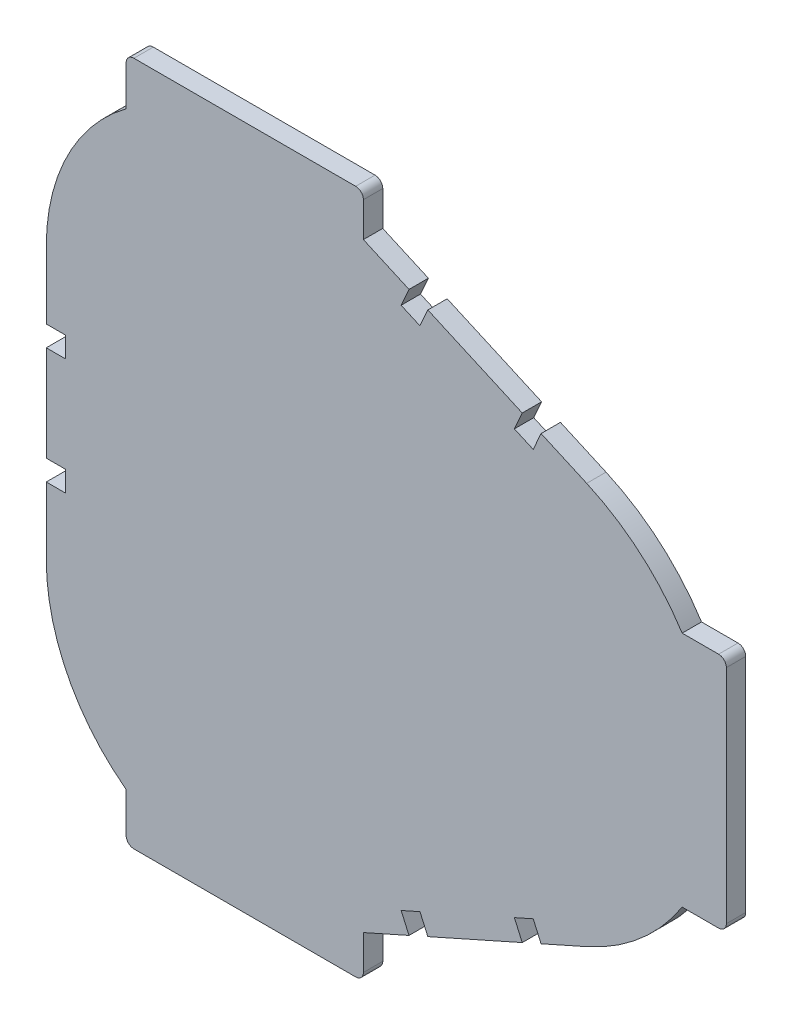
SolidWorks part; units mm, degrees
ref_plane "Front Plane" through (0, 0, 0) normal (0, 0, 1) x (1, 0, 0)
ref_plane "Top Plane" through (0, 0, 0) normal (0, 1, 0) x (1, 0, 0)
ref_plane "Right Plane" through (0, 0, 0) normal (1, 0, 0) x (0, 0, -1)
sketch "Sketch1" plane through (0, 0, -130.81) normal (0, 0, -1) x (-1, 0, 0)
  line L0 (76.8768, 62.4132) -> (76.8768, 49.4592) construction
  line L1 (76.8768, 49.4592) -> (83.2268, 49.4592) construction
  line L2 (83.2268, 49.4592) -> (83.2268, 62.4132) construction
  line L3 (83.2268, 62.4132) -> (76.8768, 62.4132) construction
  line L4 (76.8768, 24.3132) -> (76.8768, 11.3592) construction
  line L5 (76.8768, 11.3592) -> (83.2268, 11.3592) construction
  line L6 (83.2268, 11.3592) -> (83.2268, 24.3132) construction
  line L7 (83.2268, 24.3132) -> (76.8768, 24.3132) construction
  line L8 (83.2268, 52.558) -> (76.8768, 52.558) construction
  line L9 (76.8768, 52.558) -> (76.8768, 21.2144) construction
  line L10 (76.8768, 21.2144) -> (83.2268, 21.2144) construction
  line L11 (83.2268, 21.2144) -> (83.2268, 52.558) construction
  line L12 (-14.4045, -69.017) -> (-14.4045, -59.0193) construction
  line L13 (-15.9112, -56.6989) -> (-33.1241, -49.0339) construction
  line L14 (-33.1241, -49.0339) -> (-35.7072, -54.8347) construction
  line L15 (-35.7072, -54.8347) -> (-20.7545, -61.4933) construction
  line L16 (-20.7545, -61.4933) -> (-20.7545, -72.827) construction
  line L17 (-18.2145, -75.367) -> (54.493, -75.367) construction
  line L18 (57.033, -72.827) -> (57.033, -59.7525) construction
  line L19 (83.2268, -7.5638) -> (83.2268, 14.458) construction
  line L20 (83.2268, 14.458) -> (76.8768, 14.458) construction
  line L21 (76.8768, 14.458) -> (76.8768, -7.5638) construction
  line L22 (50.683, -57.8039) -> (50.683, -69.017) construction
  line L23 (50.683, -69.017) -> (-14.4045, -69.017) construction
  line L24 (-42.127, -45.0248) -> (-44.7101, -50.8256) construction
  line L25 (-44.7101, -50.8256) -> (-32.8764, -56.0953) construction
  line L26 (-32.8764, -56.0953) -> (-30.2932, -50.2945) construction
  line L27 (-30.2932, -50.2945) -> (-42.127, -45.0248) construction
  line L28 (-79.2523, -28.4925) -> (-81.8355, -34.2934) construction
  line L29 (-81.8355, -34.2934) -> (-70.0018, -39.563) construction
  line L30 (-70.0018, -39.563) -> (-67.4186, -33.7622) construction
  line L31 (-67.4186, -33.7622) -> (-79.2523, -28.4925) construction
  line L32 (-39.2961, -46.2854) -> (-70.2494, -32.5016) construction
  line L33 (-70.2494, -32.5016) -> (-72.8326, -38.3024) construction
  line L34 (-72.8326, -38.3024) -> (-41.8793, -52.0862) construction
  line L35 (-41.8793, -52.0862) -> (-39.2961, -46.2854) construction
  line L36 (-125.2661, 75.7799) -> (-137.2173, 75.7799) construction
  line L37 (-139.7573, 73.2399) -> (-139.7573, 0.5324) construction
  line L38 (-137.2173, -2.0076) -> (-125.2661, -2.0076) construction
  line L39 (-93.9575, -28.8953) -> (-79.0047, -35.554) construction
  line L40 (-79.0047, -35.554) -> (-76.4215, -29.7531) construction
  line L41 (-76.4215, -29.7531) -> (-91.3743, -23.0945) construction
  line L42 (-123.1471, 4.3424) -> (-130.8673, 4.3424) construction
  line L43 (-133.4073, 6.8824) -> (-133.4073, 66.8899) construction
  line L44 (-130.8673, 69.4299) -> (-123.1471, 69.4299) construction
  line L45 (-91.3743, 96.8669) -> (-76.4215, 103.5255) construction
  line L46 (-76.4215, 103.5255) -> (-79.0047, 109.3263) construction
  line L47 (-79.0047, 109.3263) -> (-93.9575, 102.6677) construction
  line L48 (-79.2523, 102.2649) -> (-67.4186, 107.5345) construction
  line L49 (-67.4186, 107.5345) -> (-70.0018, 113.3354) construction
  line L50 (-70.0018, 113.3354) -> (-81.8355, 108.0657) construction
  line L51 (-81.8355, 108.0657) -> (-79.2523, 102.2649) construction
  line L52 (-72.8326, 112.0748) -> (-70.2494, 106.274) construction
  line L53 (-70.2494, 106.274) -> (-39.2961, 120.0578) construction
  line L54 (-39.2961, 120.0578) -> (-41.8793, 125.8586) construction
  line L55 (-41.8793, 125.8586) -> (-72.8326, 112.0748) construction
  line L56 (-42.127, 118.7972) -> (-30.2932, 124.0668) construction
  line L57 (-30.2932, 124.0668) -> (-32.8764, 129.8677) construction
  line L58 (-32.8764, 129.8677) -> (-44.7101, 124.598) construction
  line L59 (-44.7101, 124.598) -> (-42.127, 118.7972) construction
  line L60 (-33.1241, 122.8062) -> (-15.9112, 130.4713) construction
  line L61 (-14.4045, 132.7916) -> (-14.4045, 140.2493) construction
  line L62 (-11.8645, 142.7893) -> (48.143, 142.7893) construction
  line L63 (50.683, 140.2493) -> (50.683, 131.5762) construction
  line L64 (76.8768, 81.3362) -> (76.8768, 59.3144) construction
  line L65 (76.8768, 59.3144) -> (83.2268, 59.3144) construction
  line L66 (83.2268, 59.3144) -> (83.2268, 81.3362) construction
  line L67 (57.033, 133.5249) -> (57.033, 146.5993) construction
  line L68 (54.493, 149.1393) -> (-18.2145, 149.1393) construction
  line L69 (-20.7545, 146.5993) -> (-20.7545, 135.2657) construction
  line L70 (-20.7545, 135.2657) -> (-35.7072, 128.6071) construction
  line L71 (-35.7072, 128.6071) -> (-33.1241, 122.8062) construction
  line L72 (76.8768, 62.4132) -> (76.8768, 49.4592)
  line L73 (76.8768, 49.4592) -> (83.2268, 49.4592)
  line L74 (83.2268, 49.4592) -> (83.2268, 62.4132)
  line L75 (83.2268, 62.4132) -> (76.8768, 62.4132)
  line L76 (76.8768, 24.3132) -> (76.8768, 11.3592)
  line L77 (76.8768, 11.3592) -> (83.2268, 11.3592)
  line L78 (83.2268, 11.3592) -> (83.2268, 24.3132)
  line L79 (83.2268, 24.3132) -> (76.8768, 24.3132)
  line L80 (83.2268, 52.558) -> (76.8768, 52.558)
  line L81 (76.8768, 52.558) -> (76.8768, 21.2144)
  line L82 (76.8768, 21.2144) -> (83.2268, 21.2144)
  line L83 (83.2268, 21.2144) -> (83.2268, 52.558)
  line L84 (-14.4045, -69.017) -> (-14.4045, -59.0193)
  line L85 (-15.9112, -56.6989) -> (-33.1241, -49.0339)
  line L86 (-33.1241, -49.0339) -> (-35.7072, -54.8347)
  line L87 (-35.7072, -54.8347) -> (-20.7545, -61.4933)
  line L88 (-20.7545, -61.4933) -> (-20.7545, -72.827)
  line L89 (-18.2145, -75.367) -> (54.493, -75.367)
  line L90 (57.033, -72.827) -> (57.033, -59.7525)
  line L91 (83.2268, -7.5638) -> (83.2268, 14.458)
  line L92 (83.2268, 14.458) -> (76.8768, 14.458)
  line L93 (76.8768, 14.458) -> (76.8768, -7.5638)
  line L94 (50.683, -57.8039) -> (50.683, -69.017)
  line L95 (50.683, -69.017) -> (-14.4045, -69.017)
  line L96 (-42.127, -45.0248) -> (-44.7101, -50.8256)
  line L97 (-44.7101, -50.8256) -> (-32.8764, -56.0953)
  line L98 (-32.8764, -56.0953) -> (-30.2932, -50.2945)
  line L99 (-30.2932, -50.2945) -> (-42.127, -45.0248)
  line L100 (-79.2523, -28.4925) -> (-81.8355, -34.2934)
  line L101 (-81.8355, -34.2934) -> (-70.0018, -39.563)
  line L102 (-70.0018, -39.563) -> (-67.4186, -33.7622)
  line L103 (-67.4186, -33.7622) -> (-79.2523, -28.4925)
  line L104 (-39.2961, -46.2854) -> (-70.2494, -32.5016)
  line L105 (-70.2494, -32.5016) -> (-72.8326, -38.3024)
  line L106 (-72.8326, -38.3024) -> (-41.8793, -52.0862)
  line L107 (-41.8793, -52.0862) -> (-39.2961, -46.2854)
  line L108 (-125.2661, 75.7799) -> (-137.2173, 75.7799)
  line L109 (-139.7573, 73.2399) -> (-139.7573, 0.5324)
  line L110 (-137.2173, -2.0076) -> (-125.2661, -2.0076)
  line L111 (-93.9575, -28.8953) -> (-79.0047, -35.554)
  line L112 (-79.0047, -35.554) -> (-76.4215, -29.7531)
  line L113 (-76.4215, -29.7531) -> (-91.3743, -23.0945)
  line L114 (-123.1471, 4.3424) -> (-130.8673, 4.3424)
  line L115 (-133.4073, 6.8824) -> (-133.4073, 66.8899)
  line L116 (-130.8673, 69.4299) -> (-123.1471, 69.4299)
  line L117 (-91.3743, 96.8669) -> (-76.4215, 103.5255)
  line L118 (-76.4215, 103.5255) -> (-79.0047, 109.3263)
  line L119 (-79.0047, 109.3263) -> (-93.9575, 102.6677)
  line L120 (-79.2523, 102.2649) -> (-67.4186, 107.5345)
  line L121 (-67.4186, 107.5345) -> (-70.0018, 113.3354)
  line L122 (-70.0018, 113.3354) -> (-81.8355, 108.0657)
  line L123 (-81.8355, 108.0657) -> (-79.2523, 102.2649)
  line L124 (-72.8326, 112.0748) -> (-70.2494, 106.274)
  line L125 (-70.2494, 106.274) -> (-39.2961, 120.0578)
  line L126 (-39.2961, 120.0578) -> (-41.8793, 125.8586)
  line L127 (-41.8793, 125.8586) -> (-72.8326, 112.0748)
  line L128 (-42.127, 118.7972) -> (-30.2932, 124.0668)
  line L129 (-30.2932, 124.0668) -> (-32.8764, 129.8677)
  line L130 (-32.8764, 129.8677) -> (-44.7101, 124.598)
  line L131 (-44.7101, 124.598) -> (-42.127, 118.7972)
  line L132 (-33.1241, 122.8062) -> (-15.9112, 130.4713)
  line L133 (-14.4045, 132.7916) -> (-14.4045, 140.2493)
  line L134 (-11.8645, 142.7893) -> (48.143, 142.7893)
  line L135 (50.683, 140.2493) -> (50.683, 131.5762)
  line L136 (76.8768, 81.3362) -> (76.8768, 59.3144)
  line L137 (76.8768, 59.3144) -> (83.2268, 59.3144)
  line L138 (83.2268, 59.3144) -> (83.2268, 81.3362)
  line L139 (57.033, 133.5249) -> (57.033, 146.5993)
  line L140 (54.493, 149.1393) -> (-18.2145, 149.1393)
  line L141 (-20.7545, 146.5993) -> (-20.7545, 135.2657)
  line L142 (-20.7545, 135.2657) -> (-35.7072, 128.6071)
  line L143 (-35.7072, 128.6071) -> (-33.1241, 122.8062)
  arc A0 (-14.4045, -59.0193) -> (-15.9112, -56.6989) centre (-16.9445, -59.0193) ccw construction
  arc A1 (-20.7545, -72.827) -> (-18.2145, -75.367) centre (-18.2145, -72.827) ccw construction
  arc A2 (54.493, -75.367) -> (57.033, -72.827) centre (54.493, -72.827) ccw construction
  arc A3 (57.033, -59.7525) -> (83.2268, -7.5638) centre (18.1393, -7.5638) ccw construction
  arc A4 (51.7688, -55.7214) -> (76.8768, -7.5638) centre (18.1393, -7.5638) ccw construction
  arc A5 (51.7688, -55.7214) -> (50.683, -57.8039) centre (53.223, -57.8039) ccw construction
  arc A6 (-137.2173, 75.7799) -> (-139.7573, 73.2399) centre (-137.2173, 73.2399) ccw construction
  arc A7 (-139.7573, 0.5324) -> (-137.2173, -2.0076) centre (-137.2173, 0.5324) ccw construction
  arc A8 (-125.2661, -2.0076) -> (-93.9575, -28.8953) centre (-64.6643, 36.8862) ccw construction
  arc A9 (-120.969, 3.1091) -> (-91.3743, -23.0945) centre (-64.6643, 36.8862) ccw construction
  arc A10 (-120.969, 3.1091) -> (-123.1471, 4.3424) centre (-123.1471, 1.8024) ccw construction
  arc A11 (-133.4073, 6.8824) -> (-130.8673, 4.3424) centre (-130.8673, 6.8824) ccw construction
  arc A12 (-130.8673, 69.4299) -> (-133.4073, 66.8899) centre (-130.8673, 66.8899) ccw construction
  arc A13 (-123.1471, 69.4299) -> (-120.969, 70.6633) centre (-123.1471, 71.9699) ccw construction
  arc A14 (-91.3743, 96.8669) -> (-120.969, 70.6633) centre (-64.6643, 36.8862) ccw construction
  arc A15 (-93.9575, 102.6677) -> (-125.2661, 75.7799) centre (-64.6643, 36.8862) ccw construction
  arc A16 (-15.9112, 130.4713) -> (-14.4045, 132.7916) centre (-16.9445, 132.7916) ccw construction
  arc A17 (-11.8645, 142.7893) -> (-14.4045, 140.2493) centre (-11.8645, 140.2493) ccw construction
  arc A18 (50.683, 140.2493) -> (48.143, 142.7893) centre (48.143, 140.2493) ccw construction
  arc A19 (50.683, 131.5762) -> (51.7688, 129.4937) centre (53.223, 131.5762) ccw construction
  arc A20 (76.8768, 81.3362) -> (51.7688, 129.4937) centre (18.1393, 81.3362) ccw construction
  arc A21 (83.2268, 81.3362) -> (57.033, 133.5249) centre (18.1393, 81.3362) ccw construction
  arc A22 (57.033, 146.5993) -> (54.493, 149.1393) centre (54.493, 146.5993) ccw construction
  arc A23 (-18.2145, 149.1393) -> (-20.7545, 146.5993) centre (-18.2145, 146.5993) ccw construction
  arc A24 (-14.4045, -59.0193) -> (-15.9112, -56.6989) centre (-16.9445, -59.0193) ccw
  arc A25 (-20.7545, -72.827) -> (-18.2145, -75.367) centre (-18.2145, -72.827) ccw
  arc A26 (54.493, -75.367) -> (57.033, -72.827) centre (54.493, -72.827) ccw
  arc A27 (57.033, -59.7525) -> (83.2268, -7.5638) centre (18.1393, -7.5638) ccw
  arc A28 (51.7688, -55.7214) -> (76.8768, -7.5638) centre (18.1393, -7.5638) ccw
  arc A29 (51.7688, -55.7214) -> (50.683, -57.8039) centre (53.223, -57.8039) ccw
  arc A30 (-137.2173, 75.7799) -> (-139.7573, 73.2399) centre (-137.2173, 73.2399) ccw
  arc A31 (-139.7573, 0.5324) -> (-137.2173, -2.0076) centre (-137.2173, 0.5324) ccw
  arc A32 (-125.2661, -2.0076) -> (-93.9575, -28.8953) centre (-64.6643, 36.8862) ccw
  arc A33 (-120.969, 3.1091) -> (-91.3743, -23.0945) centre (-64.6643, 36.8862) ccw
  arc A34 (-120.969, 3.1091) -> (-123.1471, 4.3424) centre (-123.1471, 1.8024) ccw
  arc A35 (-133.4073, 6.8824) -> (-130.8673, 4.3424) centre (-130.8673, 6.8824) ccw
  arc A36 (-130.8673, 69.4299) -> (-133.4073, 66.8899) centre (-130.8673, 66.8899) ccw
  arc A37 (-123.1471, 69.4299) -> (-120.969, 70.6633) centre (-123.1471, 71.9699) ccw
  arc A38 (-91.3743, 96.8669) -> (-120.969, 70.6633) centre (-64.6643, 36.8862) ccw
  arc A39 (-93.9575, 102.6677) -> (-125.2661, 75.7799) centre (-64.6643, 36.8862) ccw
  arc A40 (-15.9112, 130.4713) -> (-14.4045, 132.7916) centre (-16.9445, 132.7916) ccw
  arc A41 (-11.8645, 142.7893) -> (-14.4045, 140.2493) centre (-11.8645, 140.2493) ccw
  arc A42 (50.683, 140.2493) -> (48.143, 142.7893) centre (48.143, 140.2493) ccw
  arc A43 (50.683, 131.5762) -> (51.7688, 129.4937) centre (53.223, 131.5762) ccw
  arc A44 (76.8768, 81.3362) -> (51.7688, 129.4937) centre (18.1393, 81.3362) ccw
  arc A45 (83.2268, 81.3362) -> (57.033, 133.5249) centre (18.1393, 81.3362) ccw
  arc A46 (57.033, 146.5993) -> (54.493, 149.1393) centre (54.493, 146.5993) ccw
  arc A47 (-18.2145, 149.1393) -> (-20.7545, 146.5993) centre (-18.2145, 146.5993) ccw
  line M24 (-125.2661, 75.7799) -> (-137.2173, 75.7799)
  arc M25 (-137.2173, 75.7799) -> (-139.7573, 73.2399) centre (-137.2173, 73.2399) ccw
  line M26 (-139.7573, 73.2399) -> (-139.7573, 0.5324)
  arc M27 (-139.7573, 0.5324) -> (-137.2173, -2.0076) centre (-137.2173, 0.5324) ccw
  line M28 (-137.2173, -2.0076) -> (-125.2661, -2.0076)
  arc M29 (-125.2661, -2.0076) -> (-93.9575, -28.8953) centre (-64.6643, 36.8862) ccw
  line M30 (-93.9575, -28.8953) -> (-79.0047, -35.554)
  line M31 (-79.0047, -35.554) -> (-76.4215, -29.7531)
  line M32 (-76.4215, -29.7531) -> (-91.3743, -23.0945)
  arc M33 (-91.3743, -23.0945) -> (-120.969, 3.1091) centre (-64.6643, 36.8862) cw
  arc M34 (-120.969, 3.1091) -> (-123.1471, 4.3424) centre (-123.1471, 1.8024) ccw
  line M35 (-123.1471, 4.3424) -> (-130.8673, 4.3424)
  arc M36 (-130.8673, 4.3424) -> (-133.4073, 6.8824) centre (-130.8673, 6.8824) cw
  line M37 (-133.4073, 6.8824) -> (-133.4073, 66.8899)
  arc M38 (-133.4073, 66.8899) -> (-130.8673, 69.4299) centre (-130.8673, 66.8899) cw
  line M39 (-130.8673, 69.4299) -> (-123.1471, 69.4299)
  arc M40 (-123.1471, 69.4299) -> (-120.969, 70.6633) centre (-123.1471, 71.9699) ccw
  arc M41 (-120.969, 70.6633) -> (-91.3743, 96.8669) centre (-64.6643, 36.8862) cw
  line M42 (-91.3743, 96.8669) -> (-76.4215, 103.5255)
  line M43 (-76.4215, 103.5255) -> (-79.0047, 109.3263)
  line M44 (-79.0047, 109.3263) -> (-93.9575, 102.6677)
  arc M45 (-93.9575, 102.6677) -> (-125.2661, 75.7799) centre (-64.6643, 36.8862) ccw
extrude "Boss-Extrude1" add sketch "Sketch1" along normal blind 6.35 contours L136 A44 A43 L135 A42 L134 A41 L133 A40 L132 L128 L125 L120 L117 L103 L104 L99 L85 A24 L84 L95 L94 A29 A28 L93 L76 L81 L72 M42 M41 M40 M39 M38 M37 M36 M35 M34 M33 M32 | L72 L137 L74 L75 | L140 A47 L141 L142 L129 L132 A40 L133 A41 L134 A42 L135 A43 A44 L136 L75 L138 A45 L139 A46 | L74 L80 L72 L73 | L79 L83 L73 L81 | L76 L82 L78 L79 | L78 L92 L76 L77 | A28 A29 L94 L95 L84 A24 L85 L98 L87 L88 A25 L89 A26 L90 A27 L91 L77 L93 | L87 L98 L85 L86 | L97 L107 L99 L96 | L102 L106 L96 L104 | L103 L105 L101 L102 | L123 L119 L100 M45 M24 M25 M26 M27 M28 M29 M30 M32 M33 M34 M35 M36 M37 M38 M39 M40 M41 M42 | L100 M32 M30 M31 | L131 L127 L121 L125 | L127 L131 L125 L126 | L130 L143 L128 L129 | L122 L124 L120 L121 | L123 L117 M44 M43 region at (-80.0518, 60.8638, -130.81) region at (-78.326, 71.8747, -130.81) region at (14.7823, 36.8775, -130.81) region at (-80.0518, 51.0086, -130.81) region at (-80.0518, 36.8862, -130.81) region at (-80.0518, 22.7638, -130.81) region at (-80.0518, 12.9086, -130.81) region at (-80.0518, 9.91, -130.81) region at (33.0002, 126.337, -130.81) region at (42.0031, 122.3279, -130.81) region at (56.0644, 116.0663, -130.81) region at (70.1256, 109.8047, -130.81) region at (33.0002, -52.5646, -130.81) region at (79.1285, 105.7956, -130.81) region at (81.957, 104.5361, -130.81) region at (42.0031, -48.5555, -130.81) region at (56.0644, -42.2939, -130.81) region at (70.1256, -36.0323, -130.81) region at (79.1285, -32.0232, -130.81)
